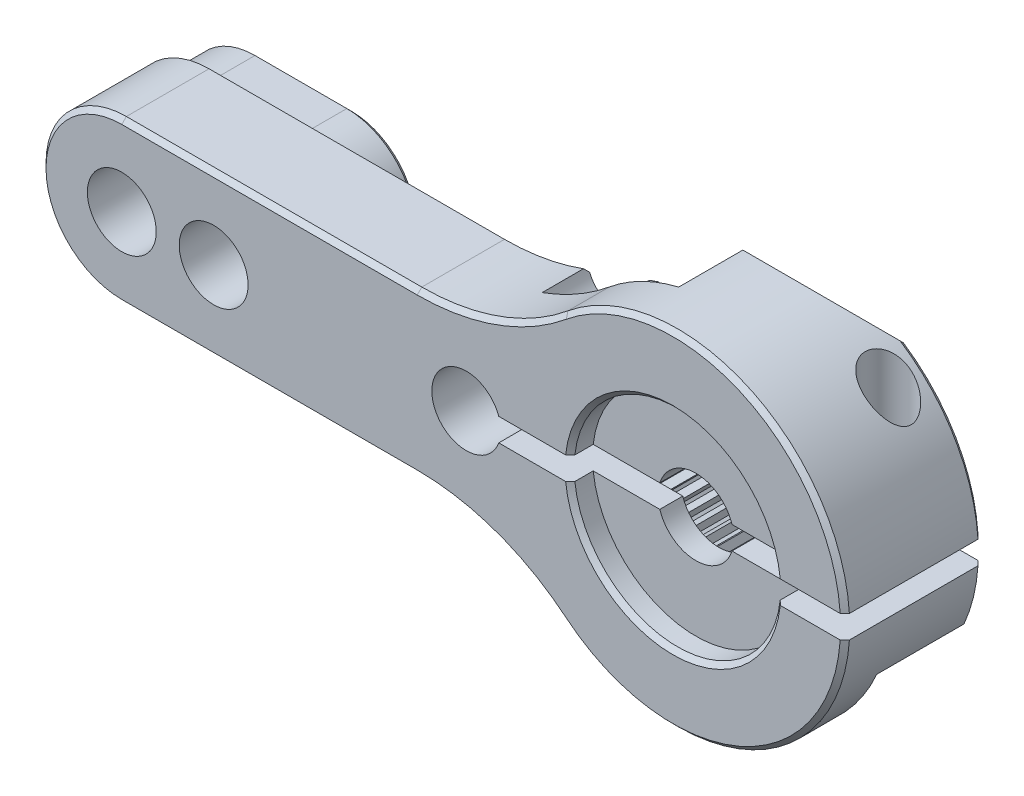
SolidWorks part; units mm, degrees
ref_plane "Plan de face" through (0, 0, 0) normal (0, 0, 1) x (1, 0, 0)
ref_plane "Plan de dessus" through (0, 0, 0) normal (0, 1, 0) x (1, 0, 0)
ref_plane "Plan de droite" through (0, 0, 0) normal (1, 0, 0) x (0, 0, -1)
sketch "Esquisse1" plane through (0, 0, 0) normal (0, 0, 1) x (1, 0, 0)
  line L0 (-11.1355, 3.5) -> (-24, 3.5)
  line L1 (-24, -3.5) -> (-11.1355, -3.5)
  line L2 (0, 0) -> (-40.4273, 0) construction
  line L3 (-27.5, 8.0474) -> (-27.5, -5.9021) construction
  line L4 (7.5, 11.0169) -> (7.5, -8.8025) construction
  circle A1 centre (0, 0) radius 1.65
  arc A2 (-4.7724, 5.7857) -> (-4.7724, -5.7857) centre (0, 0) cw
  arc A3 (-24, 3.5) -> (-24, -3.5) centre (-24, 0) ccw
  arc A4 (-11.1355, -3.5) -> (-4.7724, -5.7857) centre (-11.1355, -13.5) cw
  arc A5 (-4.7724, 5.7857) -> (-11.1355, 3.5) centre (-11.1355, 13.5) cw
  circle A6 centre (-9, 0) radius 1.5
  circle A7 centre (-24, 0) radius 1.5
  circle A8 centre (-20, 0) radius 1.5
  point P14 (-6.6332, -3.5)
  point P18 (-6.6332, 3.5)
  dimension "D1" = 7.5
  dimension "D2" = 3.3
  dimension "D5" = 10
  dimension "D6" = 3
  dimension "D7" = 3
  dimension "D8" = 3
  dimension "D3" = 7
  dimension "D4" = 35
  dimension "D9" = 9
  dimension "D10" = 11
  dimension "D11" = 4
extrude "Boss.-Extru.1" add sketch "Esquisse1" along normal blind 6
sketch "Esquisse2" plane through (0, 0, 6) normal (0, 0, 1) x (1, 0, 0)
  line L0 (7.5, 0) -> (-41.9387, 0) construction
  line L1 (8.5, 0.5) -> (-10.4142, 0.5)
  line L2 (8.5, 0.5) -> (8.5, -0.5)
  line L3 (8.5, -0.5) -> (-10.4142, -0.5)
  line L4 (-10.4142, 0.5) -> (-10.4142, -0.5)
  arc A0 (-4.7724, -5.7857) -> (-4.7724, 5.7857) centre (0, 0) ccw construction
  circle A1 centre (-9, 0) radius 1.5 construction
  dimension "D1" = 1
  dimension "D2" = 1
extrude "Enlèv. mat.-Extru.1" cut sketch "Esquisse2" against normal blind 6
sketch "Esquisse3" plane through (0, 0, 0) normal (0, 0, -1) x (-1, 0, 0)
  line L2 (24, -3.5) -> (11.1355, -3.5)
  line L3 (24, -3.5) -> (11.1355, -3.5)
  line L5 (24, 0) -> (20, 0) construction
  line L6 (11.1355, 3.5) -> (24, 3.5)
  line L7 (11.1355, 3.5) -> (24, 3.5)
  line L8 (24, -3) -> (20, -3)
  line L9 (24, 3) -> (20, 3)
  arc A0 (4.7724, 5.7857) -> (4.7724, -5.7857) centre (0, 0) cw
  arc A5 (11.1355, -3.5) -> (4.7724, -5.7857) centre (11.1355, -13.5) ccw
  arc A6 (11.1355, -3.5) -> (4.7724, -5.7857) centre (11.1355, -13.5) ccw
  arc A10 (24, -3) -> (24, 3) centre (24, 0) ccw
  arc A11 (20, 3) -> (20, -3) centre (20, 0) ccw
  arc A12 (24, -3.5) -> (24, 3.5) centre (24, 0) ccw
  arc A13 (4.7724, 5.7857) -> (11.1355, 3.5) centre (11.1355, 13.5) ccw
  arc A14 (24, -3.5) -> (24, 3.5) centre (24, 0) ccw
  arc A15 (4.7724, 5.7857) -> (11.1355, 3.5) centre (11.1355, 13.5) ccw
  point P5 (22, 0)
  dimension "D3" = 4
  dimension "D4" = 0.5
  dimension "D1" = 0
  dimension "D2" = 0
extrude "Enlèv. mat.-Extru.2" cut sketch "Esquisse3" against normal blind 2
sketch "Esquisse4" plane through (0, 0, 0) normal (0, 0, -1) x (-1, 0, 0)
  line L0 (-7.5, -3) -> (-3.25, -3)
  line L1 (-1.75, -4.5) -> (-1.75, -7.5)
  line L2 (-1.75, -7.5) -> (-7.5, -7.5)
  line L3 (-7.5, -7.5) -> (-7.5, -3)
  line L4 (-1.5724, -0.5) -> (-7.4833, -0.5) construction
  line L5 (1.5724, 0.5) -> (7.4833, 0.5) construction
  line L6 (1.75, 7.5) -> (7.75, 7.5)
  line L7 (1.75, 7.5) -> (1.75, 4.5)
  line L8 (3.25, 3) -> (6.25, 3)
  line L9 (7.75, 7.5) -> (7.75, 4.5)
  arc A0 (7.4833, 0.5) -> (-7.4833, 0.5) centre (0, 0) ccw construction
  arc A1 (-7.4833, -0.5) -> (7.4833, -0.5) centre (0, 0) ccw construction
  arc A2 (-3.25, -3) -> (-1.75, -4.5) centre (-3.25, -4.5) cw
  arc A3 (6.25, 3) -> (7.75, 4.5) centre (6.25, 4.5) ccw
  arc A4 (1.75, 4.5) -> (3.25, 3) centre (3.25, 4.5) ccw
  point P14 (-1.75, -3)
  dimension "D3" = 1.5
  dimension "D7" = 1.5
  dimension "D1" = 5.75
  dimension "D2" = 2.5
  dimension "D4" = 3.5
  dimension "D5" = 2.5
  dimension "D6" = 6
extrude "Enlèv. mat.-Extru.3" cut sketch "Esquisse4" against normal blind 4
sketch "Esquisse5" plane through (0, -3, 0) normal (0, -1, 0) x (1, 0, 0)
  line L0 (3.25, 4) -> (6.8739, 4) construction
  line L2 (6.8739, 4) -> (6.8739, 0) construction
  circle A0 centre (4.8739, 1.5) radius 1
  dimension "D1" = 2
  dimension "D2" = 2.5
  dimension "D3" = 2
extrude "Enlèv. mat.-Extru.4" cut sketch "Esquisse5" against normal through all
sketch "Esquisse6" plane through (0, 3, 0) normal (0, 1, 0) x (1, 0, 0)
  line L0 (-7.4833, -2) -> (-7.4833, 0) construction
  line L1 (4.8739, -1.5) -> (-10.9129, -1.5) construction
  circle A0 centre (-5.2333, -1.5) radius 1
  dimension "D1" = 2
  dimension "D2" = 2.25
extrude "Enlèv. mat.-Extru.5" cut sketch "Esquisse6" against normal through all
sketch "Esquisse7" plane through (0, 0, 0) normal (1, 0, 0) x (0, 0, -1)
  line L0 (-1.4142, 7.5) -> (0, 6.0858)
  line L1 (0, 7.5) -> (-6, 7.5) construction
  line L2 (0, 0.5) -> (0, 7.5) construction
  line L3 (0, 6.0858) -> (0, 7.5)
  line L4 (0, 7.5) -> (-1.4142, 7.5)
  line L5 (0, -6.0858) -> (-1.4142, -7.5)
  line L6 (0, -7.293) -> (0, -4.5) construction
  line L7 (-1.4142, -7.5) -> (0, -7.5)
  line L8 (0, -7.5) -> (0, -6.0858)
  line L9 (0, -7.5) -> (0, -0.5) construction
  dimension "D1" = 2
  dimension "D2" = 45
  dimension "D3" = 45
  dimension "D4" = 2
  dimension "D5" = 15
extrude "Enlèv. mat.-Extru.6" cut sketch "Esquisse7" against normal blind 10 and the other way blind 10
sketch "Esquisse8" plane through (0, 0, 0) normal (0, 0, -1) x (-1, 0, 0)
  circle A0 centre (0, 0) radius 3
  dimension "D1" = 6
extrude "Enlèv. mat.-Extru.7" cut sketch "Esquisse8" against normal blind 4
sketch "Esquisse9" plane through (0, 0, 0) normal (0, 0, -1) x (-1, 0, 0)
  line L0 (0, 0) -> (0, 3.5855) construction
  line L1 (-0.8887, 3) -> (1.1976, 3) construction
  line L2 (-0.2021, 3) -> (0, 2.65)
  line L3 (0, 2.65) -> (0.2021, 3)
  line L4 (0.2021, 3) -> (-0.2021, 3)
  arc A0 (2.958, 0.5) -> (-2.958, 0.5) centre (0, 0) ccw construction
  dimension "D1" = 30
  dimension "D2" = 0.35
extrude "Boss.-Extru.2" add sketch "Esquisse9" against normal up to surface (4 mm away) up to face at (0, 1.4125, 4)
pattern_circular "Répétition circulaire1" count 36 over 360 about axis through (0, 0, 4) along (0, 0, -1) skipping 9, 27 of "Boss.-Extru.2"
sketch "Esquisse10" plane through (0, 0, 0) normal (0, 0, -1) x (-1, 0, 0)
  line L0 (7.4833, -0.5) -> (2.9581, -0.5) construction
  line L1 (-7.4833, 0.5) -> (3.8917, 0.5)
  line L2 (-7.4833, 0.5) -> (-7.4833, -0.5)
  line L3 (-7.4833, -0.5) -> (3.8917, -0.5)
  line L4 (3.8917, 0.5) -> (3.8917, -0.5)
extrude "Enlèv. mat.-Extru.8" cut sketch "Esquisse10" against normal through all
chamfer "Chanfrein1" distance 0.2 angle 45 20 edges at (2.9702, 6.8868, 6) (-7.7549, 4.0888, 6) (-17.5678, 3.5, 6) (-27.5, 0, 6) (-17.5678, -3.5, 6) (2.9702, -6.8868, 6) (-7.7549, -4.0888, 6) (-22, 3, 0) (-17, 0, 0) (-27, 0, 0) (-22, -3, 0) (-9.3901, 3.6535, 2) (-17.5678, 3.5, 2) (-27.5, 0, 2) (-17.5678, -3.5, 2) (-8.5271, -3.8462, 2) (7.2866, -1.7763, 0) (6.5578, 3.6395, 0) (-7.2716, 1.8368, 0) (-6.5578, -3.6395, 0)
sketch "Esquisse11" plane through (0, 0, 6) normal (0, 0, 1) x (1, 0, 0)
  circle A0 centre (0, 0) radius 4.5
  dimension "D1" = 9
extrude "Enlèv. mat.-Extru.9" cut sketch "Esquisse11" against normal blind 1
chamfer "Chanfrein2" distance 0.2 angle 45 2 edges at (0, -4.5, 6) (0, 4.5, 6)
